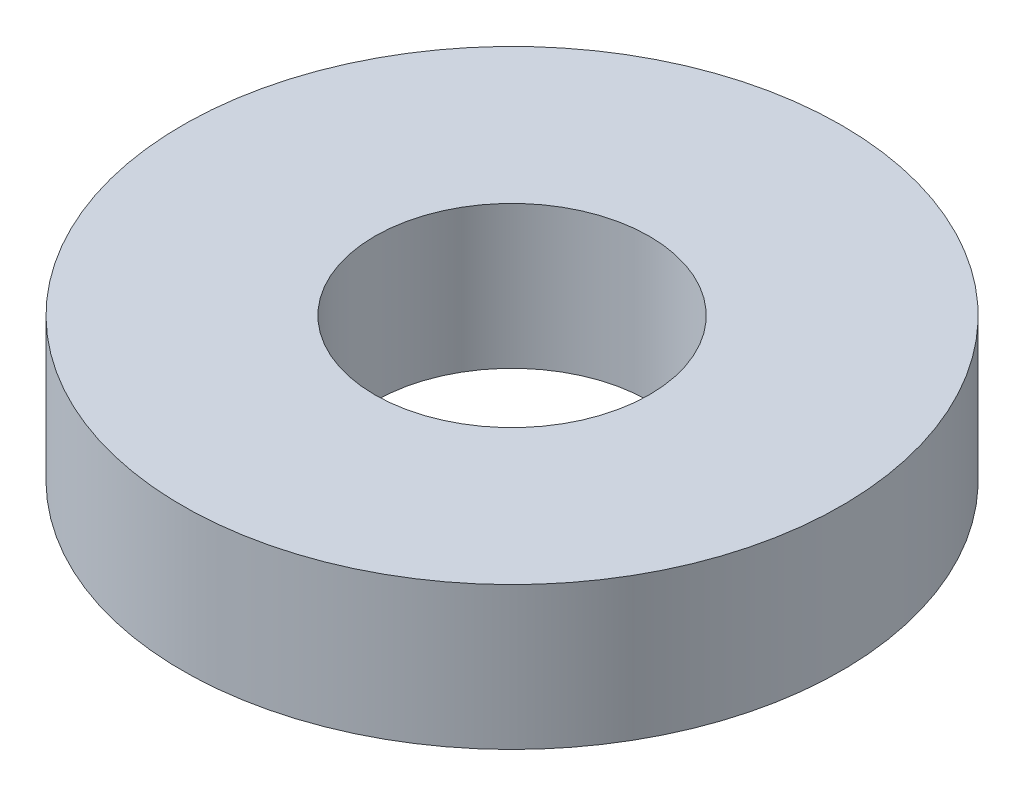
SolidWorks part; units mm, degrees
ref_plane "Front Plane" through (0, 0, 0) normal (0, 0, 1) x (1, 0, 0)
ref_plane "Top Plane" through (0, 0, 0) normal (0, 1, 0) x (1, 0, 0)
ref_plane "Right Plane" through (0, 0, 0) normal (1, 0, 0) x (0, 0, -1)
sketch "Sketch1" plane through (0, 0, 0) normal (0, 1, 0) x (1, 0, 0)
  circle A0 centre (0, 0) radius 30
  dimension "FLANGE_OD" = 60
extrude "Boss-Extrude1" add sketch "Sketch1" along normal blind 13
sketch "Sketch2" plane through (0, 0, 0) normal (0, 1, 0) x (1, 0, 0)
  circle A0 centre (0, 0) radius 12.5
  dimension "BORE_D" = 25
extrude "Cut-Extrude1" cut sketch "Sketch2" along normal through all
sketch "Sketch3" plane through (0, 13, 0) normal (0, 1, 0) x (1, 0, 0)
  circle A0 centre (0, 0) radius 10.0834 construction
  circle A1 centre (-10.0834, 0) radius 1.8643
  dimension "BOLT_D" = 3.7286
  dimension "BOLT_PCD" = 20.1669
extrude "Cut-Extrude2" cut sketch "Sketch3" against normal blind 7.9264 rebuild error yes
pattern_circular "CirPattern1" count 4 over 360 rebuild error yes
